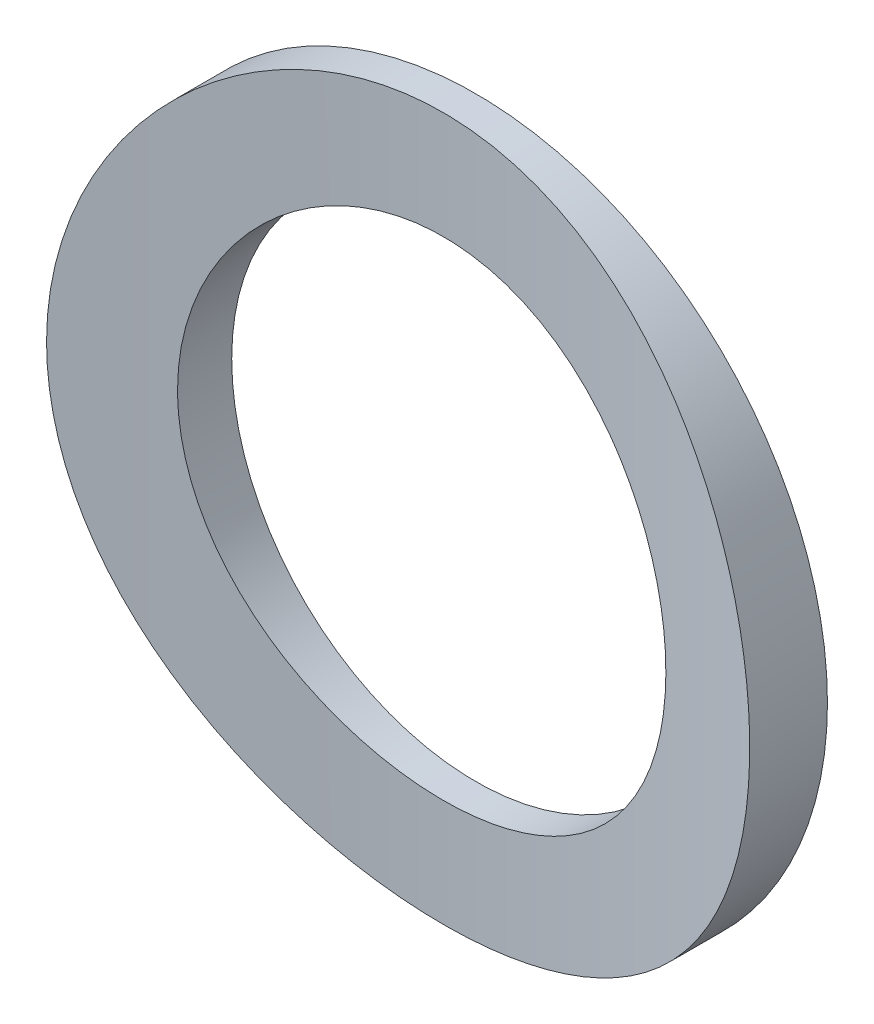
SolidWorks part; units mm, degrees
material "PTFE (general)"
ref_plane "Front Plane" through (0, 0, 0) normal (0, 0, 1) x (1, 0, 0)
ref_plane "Top Plane" through (0, 0, 0) normal (0, 1, 0) x (1, 0, 0)
ref_plane "Right Plane" through (0, 0, 0) normal (1, 0, 0) x (0, 0, -1)
sketch "Sketch1" plane through (0, 0, 0) normal (0, 0, 1) x (1, 0, 0)
  circle A0 centre (0, 0) radius 10.8
  circle A1 centre (0, 0) radius 7.5
  dimension "D1" = 21.6
  dimension "D2" = 15
extrude "Boss-Extrude1" add sketch "Sketch1" along normal blind 30
sketch "Sketch2" plane through (0, 0, 0) normal (0, 1, 0) x (1, 0, 0)
  line L0 (10.8, 0) -> (-10.8, 0) construction
  circle A0 centre (0, -43.725) radius 42.725
  dimension "D1" = 85.45
  dimension "D2" = 43.725
extrude "Cut-Extrude1" cut sketch "Sketch2" against normal through all both and the other way through all
